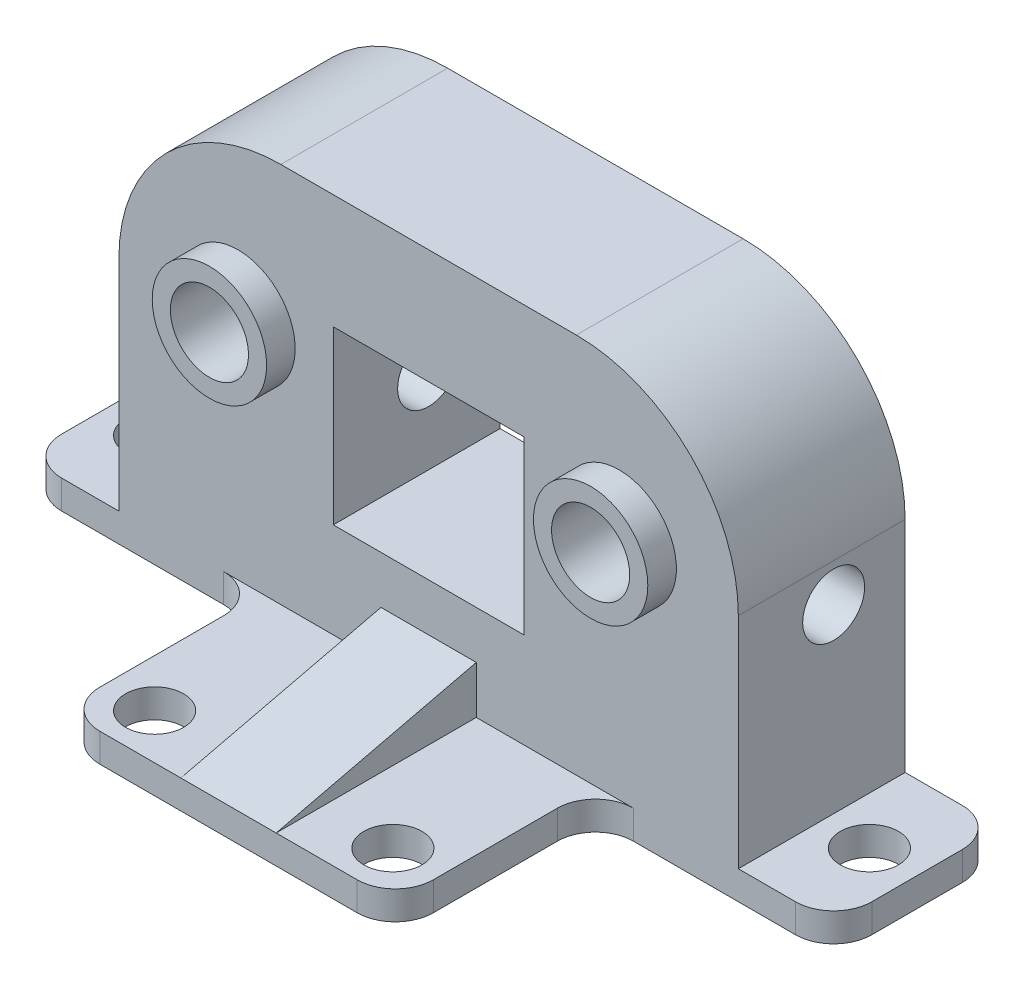
SolidWorks part; units mm, degrees
ref_plane "Přední rovina" through (0, 0, 0) normal (0, 0, 1) x (1, 0, 0)
ref_plane "Vrchní rovina" through (0, 0, 0) normal (0, 1, 0) x (1, 0, 0)
ref_plane "Pravá rovina" through (0, 0, 0) normal (1, 0, 0) x (0, 0, -1)
sketch "Skica1" plane through (0, 0, 0) normal (0, 1, 0) x (1, 0, 0)
  line L1 (-42.5, 8.75) -> (42.5, 8.75)
  line L2 (-42.5, 8.75) -> (-42.5, -8.75)
  line L3 (-42.5, -8.75) -> (42.5, -8.75)
  line L4 (42.5, 8.75) -> (42.5, -8.75)
  line L5 (-42.5, 8.75) -> (42.5, -8.75) construction
  line L6 (-42.5, -8.75) -> (42.5, 8.75) construction
  line L7 (37.5, 0) -> (-37.5, 0) construction
  circle A1 centre (-37.5, 0) radius 3.05
  circle A3 centre (37.5, 0) radius 3.05
  point P0 (0, 0)
  point P8 (0, 0)
  dimension "D3" = 75
  dimension "D4" = 6.1
  dimension "D1" = 85
  dimension "D2" = 17.5
extrude "Přidat vysunutím1" add sketch "Skica1" along normal blind 3
sketch "Skica3" plane through (0, 0, 8.75) normal (0, 0, 1) x (1, 0, 0)
  line L0 (-42.5, 3) -> (42.5, 3) construction
  line L1 (-32.5, 43) -> (32.5, 43)
  line L2 (-32.5, 43) -> (-32.5, 3)
  line L3 (-32.5, 3) -> (32.5, 3)
  line L4 (32.5, 43) -> (32.5, 3)
  line L5 (-32.5, 43) -> (32.5, 3) construction
  line L6 (-32.5, 3) -> (32.5, 43) construction
  line L7 (0, 23) -> (0, 0) construction
  line L8 (-42.5, 0) -> (42.5, 0) construction
  point P0 (0, 23)
  dimension "D1" = 65
  dimension "D2" = 40
extrude "Přidat vysunutím2" add sketch "Skica3" against normal blind 17.5
fillet "Zaoblit2" radius 17 2 edges at (-32.5, 43, 0) (32.5, 43, 0)
sketch "Skica4" plane through (0, 0, 8.75) normal (0, 0, 1) x (1, 0, 0)
  line L0 (-20, 27) -> (20, 27) construction
  line L1 (-42.5, 0) -> (42.5, 0) construction
  line L2 (0, 27) -> (0, 0) construction
  circle A0 centre (-20, 27) radius 4.1
  circle A1 centre (20, 27) radius 4.1
  circle A2 centre (-20, 27) radius 6
  circle A3 centre (20, 27) radius 6
  point P6 (0, 0)
  dimension "D2" = 8.2
  dimension "D3" = 8.2
  dimension "D4" = 12
  dimension "D5" = 12
  dimension "D1" = 27
  dimension "D6" = 40
extrude "Přidat vysunutím3" add sketch "Skica4" along normal blind 3
extrude "Odebrat vysunutím1" cut sketch "Skica4<2>" against normal blind 4 contours A1 | A0 region at (-20, 27, 8.75) region at (20, 27, 8.75)
sketch "Skica4<2>" plane through (0, 0, 8.75) normal (0, 0, 1) x (1, 0, 0) same geometry as "Skica4"
sketch "Skica5" plane through (0, 0, 8.75) normal (0, 0, 1) x (1, 0, 0)
  line L0 (0, 0) -> (0, 22) construction
  line L1 (-10, 31) -> (10, 31)
  line L2 (-10, 31) -> (-10, 13)
  line L3 (-10, 13) -> (10, 13)
  line L4 (10, 31) -> (10, 13)
  line L5 (-10, 31) -> (10, 13) construction
  line L6 (-10, 13) -> (10, 31) construction
  line L7 (-42.5, 0) -> (42.5, 0) construction
  circle A0 centre (-20, 27) radius 4.1 construction
  point P0 (0, 22)
  dimension "D1" = 20
  dimension "D2" = 18
  dimension "D3" = 4
extrude "Odebrat vysunutím2" cut sketch "Skica5" against normal through all
sketch "Skica7" plane through (32.5, 0, 0) normal (1, 0, 0) x (0, 0, -1)
  line L0 (-8.75, 31) -> (-8.75, 13) construction
  line L1 (-8.75, 31) -> (-8.75, 13) construction
  line L2 (-8.75, 22) -> (11.25, 22) construction
  circle A0 centre (1.25, 22) radius 3.25
  dimension "D1" = 6.5
  dimension "D2" = 10
extrude "Odebrat vysunutím4" cut sketch "Skica7" against normal blind 50
sketch "Skica8" plane through (0, 0, 0) normal (0, -1, 0) x (1, 0, 0)
  line L0 (-17.5, 8.75) -> (-17.5, 29.75)
  line L2 (-17.5, 29.75) -> (17.5, 29.75)
  line L3 (17.5, 29.75) -> (17.5, 8.75)
  line L4 (17.5, 8.75) -> (-17.5, 8.75)
  line L5 (0, 8.75) -> (0, 0) construction
  line L6 (-42.5, 8.75) -> (42.5, 8.75) construction
  circle A0 centre (-12.5, 25) radius 3.05
  circle A1 centre (-37.5, 0) radius 3.05 construction
  circle A2 centre (-37.5, 0) radius 3.05 construction
  circle A3 centre (12.5, 25) radius 3.05
  dimension "D1" = 6.1
  dimension "D2" = 25
  dimension "D3" = 25
  dimension "D4" = 21
  dimension "D5" = 35
extrude "Přidat vysunutím4" add sketch "Skica8" against normal blind 3
fillet "Zaoblit1" radius 4 8 edges at (42.5, 1.5, 8.75) (42.5, 1.5, -8.75) (-42.5, 1.5, -8.75) (-42.5, 1.5, 8.75) (17.5, 1.5, 8.75) (-17.5, 1.5, 8.75) (-17.5, 1.5, 29.75) (17.5, 1.5, 29.75)
sketch "Skica12" plane through (0, 0, 0) normal (1, 0, 0) x (0, 0, -1)
  line L0 (-29.75, 3) -> (-8.75, 8)
  line L1 (-8.75, 26) -> (-8.75, 3) construction
  line L2 (-25.75, 3) -> (-12.75, 3) construction
  point P3 (-8.75, 9.0484)
  dimension "D1" = 5
rib "Žebro4" sketch "Skica12" sketch "Skica12" thickness 10 extrusion direction parallel to sketch draft on no parameters "D1"=10
